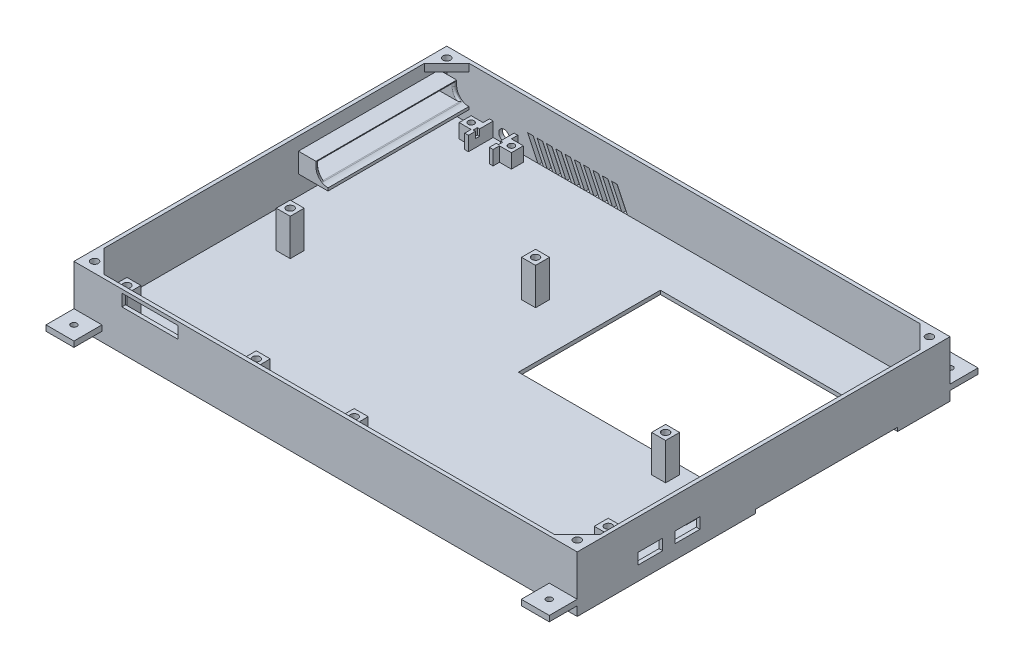
SolidWorks part; units mm, degrees
material "PLA"
ref_plane "Спереди" through (0, 0, 0) normal (0, 0, 1) x (1, 0, 0)
ref_plane "Сверху" through (0, 0, 0) normal (0, 1, 0) x (1, 0, 0)
ref_plane "Справа" through (0, 0, 0) normal (1, 0, 0) x (0, 0, -1)
sketch "Эскиз1" plane through (0, 0, 0) normal (0, 1, 0) x (1, 0, 0)
  line L1 (135, 100) -> (-135, 100)
  line L2 (135, 100) -> (135, -100)
  line L3 (135, -100) -> (-135, -100)
  line L4 (-135, 100) -> (-135, -100)
  line L5 (135, 100) -> (-135, -100) construction
  line L6 (135, -100) -> (-135, 100) construction
  point P0 (0, 0)
  dimension "D1" = 200
  dimension "D2" = 270
extrude "Бобышка-Вытянуть1" add sketch "Эскиз1" along normal blind 2
sketch "Эскиз2" plane through (0, 2, 0) normal (0, 1, 0) x (1, 0, 0)
  line L0 (133, 98) -> (-133, 98)
  line L1 (-133, 98) -> (-133, -98)
  line L2 (-133, -98) -> (-109.3, -98)
  line L3 (133, -98) -> (133, 98)
  line L4 (-135, 100) -> (-135, -100)
  line L5 (-135, -100) -> (135, -100)
  line L6 (135, -100) -> (135, 100)
  line L7 (135, 100) -> (-135, 100)
  line L8 (-135, 100) -> (-135, -100)
  line L9 (-135, -100) -> (-109.3, -100)
  line L10 (135, -100) -> (135, 100)
  line L11 (135, 100) -> (-135, 100)
  line L12 (-109.3, -98) -> (-109.3, -100)
  line L14 (-79.1, -98) -> (-79.1, -100)
  line L16 (-79.1, -98) -> (133, -98)
  line L17 (-79.1, -100) -> (135, -100)
  line L18 (-133, -98) -> (133, -98) construction
  line L20 (-135, -100) -> (135, -100) construction
  dimension "D3" = 25.7
  dimension "D4" = 55.9
  dimension "D1" = 0
  dimension "D2" = 2
extrude "Бобышка-Вытянуть2" add sketch "Эскиз2" along normal offset from surface (28 mm away) 7 offset beyond the face yes
sketch "Эскиз3" plane through (0, 2, 0) normal (0, 1, 0) x (1, 0, 0)
  line L1 (-109.3, -98) -> (-79.1, -98)
  line L2 (-109.3, -98) -> (-109.3, -100)
  line L3 (-109.3, -100) -> (-79.1, -100)
  line L4 (-79.1, -98) -> (-79.1, -100)
extrude "Бобышка-Вытянуть3" add sketch "Эскиз3" along normal blind 19.7
sketch "Эскиз4" plane through (-109.3, 0, 0) normal (1, 0, 0) x (0, 0, -1)
  line L0 (-100, 30) -> (-100, 21.7) construction
  line L1 (-98, 30) -> (-100, 30)
  line L2 (-98, 30) -> (-98, 28.1)
  line L3 (-98, 28.1) -> (-100, 28.1)
  line L4 (-100, 30) -> (-100, 28.1)
  dimension "D1" = 1.9
extrude "Бобышка-Вытянуть4" add sketch "Эскиз4" along normal up to surface (30.2 mm away) up to face at (-79.1, 25.85, 99)
sketch "Эскиз5" plane through (135, 0, 0) normal (1, 0, 0) x (0, 0, -1)
  line L0 (-100, 30) -> (-100, 0) construction
  line L1 (-54.15, 13.5) -> (-67.45, 13.5)
  line L2 (-54.15, 13.5) -> (-54.15, 7.6)
  line L3 (-54.15, 7.6) -> (-67.45, 7.6)
  line L4 (-67.45, 13.5) -> (-67.45, 7.6)
  line L5 (-54.15, 13.5) -> (-67.45, 7.6) construction
  line L6 (-54.15, 7.6) -> (-67.45, 13.5) construction
  line L7 (-34.15, 13.5) -> (-47.45, 13.5)
  line L8 (-34.15, 13.5) -> (-34.15, 7.6)
  line L9 (-34.15, 7.6) -> (-47.45, 7.6)
  line L10 (-47.45, 13.5) -> (-47.45, 7.6)
  line L11 (-34.15, 13.5) -> (-47.45, 7.6) construction
  line L12 (-34.15, 7.6) -> (-47.45, 13.5) construction
  line L13 (-100, 0) -> (100, 0) construction
  point P0 (-60.8, 10.55)
  point P5 (-40.8, 10.55)
  dimension "D1" = 13.3
  dimension "D2" = 5.9
  dimension "D3" = 6.7
  dimension "D4" = 32.55
  dimension "D5" = 13.5
extrude "Вырез-Вытянуть1" cut sketch "Эскиз5" against normal up to surface (2 mm away) up to face at (133, 16, 0)
sketch "Эскиз10" plane through (0, 2, 0) normal (0, 1, 0) x (1, 0, 0)
  line L0 (133, 98) -> (133, -98) construction
  line L1 (123.675, -22.825) -> (116.175, -22.825)
  line L2 (123.675, -22.825) -> (123.675, -30.325)
  line L3 (123.675, -30.325) -> (116.175, -30.325)
  line L4 (116.175, -22.825) -> (116.175, -30.325)
  line L5 (123.675, -22.825) -> (116.175, -30.325) construction
  line L6 (123.675, -30.325) -> (116.175, -22.825) construction
  line L7 (114.05, -54.9) -> (106.55, -54.9)
  line L8 (114.05, -54.9) -> (114.05, -62.4)
  line L9 (114.05, -62.4) -> (106.55, -62.4)
  line L10 (106.55, -54.9) -> (106.55, -62.4)
  line L11 (114.05, -54.9) -> (106.55, -62.4) construction
  line L12 (114.05, -62.4) -> (106.55, -54.9) construction
  line L13 (114.675, -87.875) -> (107.175, -87.875)
  line L14 (114.675, -87.875) -> (114.675, -95.375)
  line L15 (114.675, -95.375) -> (107.175, -95.375)
  line L16 (107.175, -87.875) -> (107.175, -95.375)
  line L17 (114.675, -87.875) -> (107.175, -95.375) construction
  line L18 (114.675, -95.375) -> (107.175, -87.875) construction
  line L19 (133, -98) -> (-133, -98) construction
  point P0 (119.925, -26.575)
  point P5 (110.3, -58.65)
  point P10 (110.925, -91.625)
  dimension "D1" = 13.075
  dimension "D2" = 71.425
  dimension "D3" = 22.7
  dimension "D4" = 39.35
  dimension "D5" = 22.075
  dimension "D6" = 6.375
  dimension "D7" = 7.5
extrude "Бобышка-Вытянуть6" add sketch "Эскиз10" along normal blind 6.9
sketch "Эскиз11" plane through (0, 2, 0) normal (0, 1, 0) x (1, 0, 0)
  line L1 (-45.3446, -84.35) -> (-52.8446, -84.35)
  line L2 (-45.3446, -84.35) -> (-45.3446, -91.85)
  line L3 (-45.3446, -91.85) -> (-52.8446, -91.85)
  line L4 (-52.8446, -84.35) -> (-52.8446, -91.85)
  line L5 (-45.3446, -84.35) -> (-52.8446, -91.85) construction
  line L6 (-45.3446, -91.85) -> (-52.8446, -84.35) construction
  line L7 (-17.6224, 30.2491) -> (-25.1224, 30.2491)
  line L8 (-17.6224, 30.2491) -> (-17.6224, 37.7491)
  line L9 (-17.6224, 37.7491) -> (-25.1224, 37.7491)
  line L10 (-25.1224, 30.2491) -> (-25.1224, 37.7491)
  line L11 (-17.6224, 30.2491) -> (-25.1224, 37.7491) construction
  line L12 (-17.6224, 37.7491) -> (-25.1224, 30.2491) construction
  line L13 (-114.1446, -92.4424) -> (-121.6446, -92.4424)
  line L14 (-114.1446, -92.4424) -> (-114.1446, -84.9424)
  line L15 (-114.1446, -84.9424) -> (-121.6446, -84.9424)
  line L16 (-121.6446, -92.4424) -> (-121.6446, -84.9424)
  line L17 (-114.1446, -92.4424) -> (-121.6446, -84.9424) construction
  line L18 (-114.1446, -84.9424) -> (-121.6446, -92.4424) construction
  line L19 (-106.25, -12.7324) -> (-113.75, -12.7324)
  line L20 (-106.25, -12.7324) -> (-106.25, -5.2324)
  line L21 (-106.25, -5.2324) -> (-113.75, -5.2324)
  line L22 (-113.75, -12.7324) -> (-113.75, -5.2324)
  line L23 (-106.25, -12.7324) -> (-113.75, -5.2324) construction
  line L24 (-106.25, -5.2324) -> (-113.75, -12.7324) construction
  line L25 (98.6279, -16.2195) -> (91.1279, -16.2195)
  line L26 (98.6279, -16.2195) -> (98.6279, -8.7195)
  line L27 (98.6279, -8.7195) -> (91.1279, -8.7195)
  line L28 (91.1279, -16.2195) -> (91.1279, -8.7195)
  line L29 (98.6279, -16.2195) -> (91.1279, -8.7195) construction
  line L30 (98.6279, -8.7195) -> (91.1279, -16.2195) construction
  line L31 (95.4554, -97.6196) -> (87.9554, -97.6196)
  line L32 (95.4554, -97.6196) -> (95.4554, -90.1196)
  line L33 (95.4554, -90.1196) -> (87.9554, -90.1196)
  line L34 (87.9554, -97.6196) -> (87.9554, -90.1196)
  line L35 (95.4554, -97.6196) -> (87.9554, -90.1196) construction
  line L36 (95.4554, -90.1196) -> (87.9554, -97.6196) construction
  line L37 (7.7554, -92.4285) -> (0.2554, -92.4285)
  line L38 (7.7554, -92.4285) -> (7.7554, -84.9285)
  line L39 (7.7554, -84.9285) -> (0.2554, -84.9285)
  line L40 (0.2554, -92.4285) -> (0.2554, -84.9285)
  line L41 (7.7554, -92.4285) -> (0.2554, -84.9285) construction
  line L42 (7.7554, -84.9285) -> (0.2554, -92.4285) construction
  line L44 (-133, 98) -> (133, 98) construction
  line L45 (-133, -98) -> (-133, 98) construction
  line L47 (133, -98) -> (-133, -98) construction
  line L48 (133, 98) -> (133, -98) construction
  point P0 (-49.0946, -88.1)
  point P5 (-21.3724, 33.9991)
  point P10 (-117.8946, -88.6924)
  point P15 (-110, -8.9824)
  point P20 (94.8779, -12.4695)
  point P25 (91.7054, -93.8696)
  point P30 (4.0054, -88.6785)
  dimension "D1" = 7.5
  dimension "D2" = 64.0009
  dimension "D3" = 111.6276
  dimension "D4" = 106.9824
  dimension "D5" = 23
  dimension "D6" = 9.3076
  dimension "D7" = 15.1054
  dimension "D8" = 9.3215
  dimension "D9" = 128.9946
  dimension "D10" = 9.9
  dimension "D11" = 83.9054
  dimension "D12" = 4.1304
  dimension "D13" = 41.2946
  dimension "D14" = 85.5305
  dimension "D15" = 38.1221
extrude "Бобышка-Вытянуть7" add sketch "Эскиз11" along normal blind 19.7
sketch "Эскиз12" plane through (0, 2, 0) normal (0, 1, 0) x (1, 0, 0)
  line L1 (135, 71.9) -> (7.7, 71.9)
  line L2 (135, 71.9) -> (135, -4.25)
  line L3 (135, -4.25) -> (7.7, -4.25)
  line L4 (7.7, 71.9) -> (7.7, -4.25)
  line L5 (-133, 98) -> (133, 98) construction
  line L6 (135, -100) -> (135, 100) construction
  dimension "D1" = 76.15
  dimension "D2" = 127.3
  dimension "D3" = 26.1
extrude "Вырез-Вытянуть2" cut sketch "Эскиз12" against normal through all
sketch "Эскиз14" plane through (0, 21.7, 0) normal (0, 1, 0) x (1, 0, 0)
  line L0 (-113.75, -5.2324) -> (-106.25, -12.7324) construction
  line L1 (-106.25, -5.2324) -> (-113.75, -12.7324) construction
  line L2 (-17.6224, 37.7491) -> (-25.1224, 30.2491) construction
  line L3 (-25.1224, 37.7491) -> (-17.6224, 30.2491) construction
  line L4 (-121.6446, -84.9424) -> (-114.1446, -92.4424) construction
  line L5 (-114.1446, -84.9424) -> (-121.6446, -92.4424) construction
  line L6 (-52.8446, -84.35) -> (-45.3446, -91.85) construction
  line L7 (-45.3446, -84.35) -> (-52.8446, -91.85) construction
  line L8 (0.2554, -84.9285) -> (7.7554, -92.4285) construction
  line L9 (7.7554, -84.9285) -> (0.2554, -92.4285) construction
  line L10 (95.4554, -90.1196) -> (87.9554, -97.6196) construction
  line L11 (95.4554, -90.1196) -> (87.9554, -90.1196) construction
  line L12 (95.4554, -90.1196) -> (95.4554, -97.6196) construction
  line L13 (95.4554, -97.6196) -> (87.9554, -97.6196) construction
  line L14 (87.9554, -90.1196) -> (87.9554, -97.6196) construction
  line L15 (95.4554, -97.6196) -> (87.9554, -90.1196) construction
  line L22 (98.6279, -8.7195) -> (91.1279, -16.2195) construction
  line L23 (98.6279, -16.2195) -> (91.1279, -8.7195) construction
  circle A0 centre (-21.3724, 33.9991) radius 2
  circle A1 centre (-110, -8.9824) radius 2
  circle A2 centre (-117.8946, -88.6924) radius 2
  circle A3 centre (-49.0946, -88.1) radius 2
  circle A4 centre (4.0054, -88.6785) radius 2
  circle A5 centre (91.7054, -93.8696) radius 2
  circle A6 centre (94.8779, -12.4695) radius 2
  dimension "D1" = 4
extrude "Вырез-Вытянуть4" cut sketch "Эскиз14" against normal blind 5
sketch "Эскиз15" plane through (0, 8.9, 0) normal (0, 1, 0) x (1, 0, 0)
  line L0 (123.675, -22.825) -> (116.175, -30.325) construction
  line L1 (116.175, -22.825) -> (123.675, -30.325) construction
  line L2 (106.55, -54.9) -> (114.05, -62.4) construction
  line L3 (114.05, -54.9) -> (106.55, -62.4) construction
  line L4 (107.175, -87.875) -> (114.675, -95.375) construction
  line L5 (114.675, -87.875) -> (107.175, -95.375) construction
  circle A0 centre (110.925, -91.625) radius 2
  circle A1 centre (110.3, -58.65) radius 2
  circle A2 centre (119.925, -26.575) radius 2
  dimension "D1" = 4
extrude "Вырез-Вытянуть5" cut sketch "Эскиз15" against normal blind 5
sketch "Эскиз16" plane through (0, 0, -100) normal (0, 0, -1) x (-1, 0, 0)
  line L0 (133, 23) -> (123.6, 23)
  line L1 (133, 30) -> (133, 2) construction
  line L2 (123.6, 23) -> (123.6, 20.4)
  line L3 (117.1, 13.9) -> (133, 13.9)
  line L4 (133, 13.9) -> (133, 23)
  line L5 (133, 2) -> (-133, 2) construction
  arc A0 (123.6, 20.4) -> (117.1, 13.9) centre (117.1, 20.4) cw
  dimension "D3" = 6.5
  dimension "D1" = 9.4
  dimension "D2" = 2.6
  dimension "D4" = 21
  dimension "D5" = 15.9
extrude "Бобышка-Вытянуть8" add sketch "Эскиз16" against normal blind 75.5 from offset 6.0824 offset against normal yes
sketch "Эскиз18" plane through (0, 0, -18.4176) normal (0, 0, 1) x (1, 0, 0)
  line L0 (-135, 22) -> (-123.6, 22)
  line L1 (-135, 30) -> (-135, 0) construction
  line L2 (-123.6, 23) -> (-123.6, 20.4) construction
  line L3 (-123.6, 22) -> (-123.6, 20.4)
  line L4 (-135, 22) -> (-135, 14.9)
  line L5 (-135, 14.9) -> (-120.5641, 14.9)
  line L6 (-133, 23) -> (-123.6, 23) construction
  line L7 (-117.1, 13.9) -> (-133, 13.9) construction
  arc A0 (-123.6, 20.4) -> (-117.1, 13.9) centre (-117.1, 20.4) ccw construction
  arc A1 (-123.6, 20.4) -> (-120.5641, 14.9) centre (-117.1, 20.4) ccw
  dimension "D1" = 1
  dimension "D2" = 1
extrude "Вырез-Вытянуть6" cut sketch "Эскиз18" against normal offset from surface (72.5 mm away) 1.5 from offset 1.5 up to face at (-126.3292, 18.5708, -93.9176) offset against normal yes
fillet "Скругление1" radius 1 6 edges at (-123.6, 21.2, -92.4176) (-123.6, 21.2, -19.9176) (-122.7906, 17.2589, -92.4176) (-120.5641, 14.9, -56.1676) (-122.7906, 17.2589, -19.9176) (-123.6, 22, -56.1676)
sketch "Эскиз19" plane through (0, 0, -18.4176) normal (0, 0, 1) x (1, 0, 0)
  line L0 (-133, 13.9) -> (-133, 12.4)
  line L1 (-133, 30) -> (-133, 2) construction
  line L2 (-133, 13.9) -> (-117.1, 13.9)
  line L3 (-117.1, 13.9) -> (-133, 13.9) construction
  line L4 (-117.1, 13.9) -> (-117.1, 12.4)
  line L5 (-117.1, 12.4) -> (-133, 12.4)
  dimension "D1" = 1.5
extrude "Бобышка-Вытянуть9" add sketch "Эскиз19" against normal up to surface (75.5 mm away) up to face at (-126.3292, 18.5708, -93.9176)
sketch "Эскиз20" plane through (0, 0, -100) normal (0, 0, -1) x (-1, 0, 0)
  line L0 (135, 30) -> (135, 0) construction
  line L1 (89.5705, 13.5) -> (86.5705, 13.5)
  line L3 (83.9, 1.5) -> (80.9, 1.5)
  line L5 (90.9, 13.5) -> (35.9, 1.5) construction
  line L6 (90.9, 1.5) -> (35.9, 13.5) construction
  line L7 (-135, 0) -> (135, 0) construction
  line L8 (35.9, 1.5) -> (41.5705, 13.5)
  line L9 (44.5705, 13.5) -> (38.9, 1.5)
  line L10 (40.9, 1.5) -> (46.5705, 13.5)
  line L11 (49.5705, 13.5) -> (43.9, 1.5)
  line L12 (45.9, 1.5) -> (51.5705, 13.5)
  line L13 (54.5705, 13.5) -> (48.9, 1.5)
  line L14 (50.9, 1.5) -> (56.5705, 13.5)
  line L15 (59.5705, 13.5) -> (53.9, 1.5)
  line L16 (55.9, 1.5) -> (61.5705, 13.5)
  line L17 (64.5705, 13.5) -> (58.9, 1.5)
  line L18 (60.9, 1.5) -> (66.5705, 13.5)
  line L19 (69.5705, 13.5) -> (63.9, 1.5)
  line L20 (65.9, 1.5) -> (71.5705, 13.5)
  line L21 (74.5705, 13.5) -> (68.9, 1.5)
  line L22 (70.9, 1.5) -> (76.5705, 13.5)
  line L23 (79.5705, 13.5) -> (73.9, 1.5)
  line L24 (75.9, 1.5) -> (81.5705, 13.5)
  line L25 (84.5705, 13.5) -> (78.9, 1.5)
  line L26 (80.9, 1.5) -> (86.5705, 13.5)
  line L27 (89.5705, 13.5) -> (83.9, 1.5)
  line L28 (44.5705, 13.5) -> (41.5705, 13.5)
  line L29 (38.9, 1.5) -> (35.9, 1.5)
  line L30 (43.9, 1.5) -> (40.9, 1.5)
  line L31 (49.5705, 13.5) -> (46.5705, 13.5)
  line L32 (54.5705, 13.5) -> (51.5705, 13.5)
  line L33 (48.9, 1.5) -> (45.9, 1.5)
  line L34 (53.9, 1.5) -> (50.9, 1.5)
  line L35 (59.5705, 13.5) -> (56.5705, 13.5)
  line L36 (58.9, 1.5) -> (55.9, 1.5)
  line L37 (64.5705, 13.5) -> (61.5705, 13.5)
  line L38 (63.9, 1.5) -> (60.9, 1.5)
  line L39 (69.5705, 13.5) -> (66.5705, 13.5)
  line L40 (68.9, 1.5) -> (65.9, 1.5)
  line L41 (74.5705, 13.5) -> (71.5705, 13.5)
  line L42 (73.9, 1.5) -> (70.9, 1.5)
  line L43 (79.5705, 13.5) -> (76.5705, 13.5)
  line L44 (78.9, 1.5) -> (75.9, 1.5)
  line L45 (84.5705, 13.5) -> (81.5705, 13.5)
  line L46 (35.9, 13.5) -> (35.9, 1.5) construction
  line L47 (90.9, 13.5) -> (90.9, 1.5) construction
  point P0 (63.4, 7.5)
  dimension "D1" = 71.6
  dimension "D2" = 1.5
  dimension "D3" = 12
  dimension "D4" = 55
  dimension "D5" = 3
  dimension "D8" = 2
  dimension "D9" = 64.707
  dimension "D6" = 10
extrude "Вырез-Вытянуть7" cut sketch "Эскиз20" against normal up to surface (2 mm away) up to face at (0, 16, -98)
sketch "Эскиз21" plane through (0, 0, -100) normal (0, 0, -1) x (-1, 0, 0)
  line L0 (135, 30) -> (135, 0) construction
  line L1 (-135, 0) -> (135, 0) construction
  circle A0 centre (102.2, 5.825) radius 2.9
  dimension "D1" = 5.8
  dimension "D2" = 32.8
  dimension "D3" = 5.825
extrude "Вырез-Вытянуть8" cut sketch "Эскиз21" against normal up to surface (2 mm away) up to face at (-57.1394, 8.5, -98)
sketch "Эскиз22" plane through (0, 2, 0) normal (0, 1, 0) x (1, 0, 0)
  line L0 (-133, 98) -> (-84.1363, 98) construction
  line L1 (-108.1, 98) -> (-110.1, 98)
  line L2 (-108.1, 98) -> (-108.1, 84.75)
  line L3 (-108.1, 84.75) -> (-110.1, 84.75)
  line L4 (-110.1, 98) -> (-110.1, 84.75)
  line L5 (-133, -98) -> (-133, 98) construction
  line L7 (-94.9, 98) -> (-96.9, 98)
  line L8 (-94.9, 98) -> (-94.9, 84.75)
  line L9 (-94.9, 84.75) -> (-96.9, 84.75)
  line L10 (-96.9, 98) -> (-96.9, 84.75)
  dimension "D1" = 24.9
  dimension "D2" = 13.25
  dimension "D3" = 2
  dimension "D4" = 36.1
extrude "Бобышка-Вытянуть10" add sketch "Эскиз22" along normal blind 7.65
sketch "Эскиз23" plane through (0, 9.65, 0) normal (0, 1, 0) x (1, 0, 0)
  line L0 (-108.1, 84.75) -> (-108.1, 98) construction
  line L1 (-108.1, 90.7) -> (-109.3, 90.7)
  line L2 (-108.1, 90.7) -> (-108.1, 88.5)
  line L3 (-108.1, 88.5) -> (-109.3, 88.5)
  line L4 (-109.3, 90.7) -> (-109.3, 88.5)
  line L5 (-96.9, 98) -> (-96.9, 84.75) construction
  line L6 (-96.9, 90.7) -> (-95.7, 90.7)
  line L7 (-96.9, 90.7) -> (-96.9, 88.5)
  line L8 (-96.9, 88.5) -> (-95.7, 88.5)
  line L9 (-95.7, 90.7) -> (-95.7, 88.5)
  line L10 (-110.1, 84.75) -> (-108.1, 84.75) construction
  dimension "D1" = 2.2
  dimension "D2" = 1.2
  dimension "D3" = 5.95
extrude "Вырез-Вытянуть9" cut sketch "Эскиз23" against normal blind 3.45
sketch "Эскиз24" plane through (0, 2, 0) normal (0, 1, 0) x (1, 0, 0)
  line L0 (-108.6, 91.375) -> (-97.4, 91.375) construction
  line L3 (-102.5, 91.875) -> (-102.5, 50091.875) construction
  line L4 (-108.1, 84.75) -> (-108.1, 98) construction
  line L5 (-108.1, 98) -> (-96.9, 98) construction
  line L6 (-110.1, 98) -> (-110.1, 84.75) construction
  line L7 (-116.5, 94.575) -> (-110.1, 94.575)
  line L8 (-116.5, 94.575) -> (-116.5, 88.175)
  line L9 (-116.5, 88.175) -> (-110.1, 88.175)
  line L10 (-110.1, 94.575) -> (-110.1, 88.175)
  line L11 (-116.5, 94.575) -> (-110.1, 88.175) construction
  line L12 (-116.5, 88.175) -> (-110.1, 94.575) construction
  line L13 (-88.5, 88.175) -> (-94.9, 88.175)
  line L14 (-94.9, 94.575) -> (-94.9, 88.175)
  line L15 (-88.5, 94.575) -> (-94.9, 94.575)
  line L16 (-88.5, 94.575) -> (-88.5, 88.175)
  circle A0 centre (-113.3, 91.375) radius 1.7 construction
  point P3 (-108.1, 91.375)
  point P8 (-102.5, 98)
  point P10 (-113.3, 91.375)
  dimension "D1" = 3.4
  dimension "D2" = 1.5
extrude "Бобышка-Вытянуть11" add sketch "Эскиз24" along normal up to surface (7.65 mm away) up to face at (-108.9, 9.65, -90.4875)
sketch "Эскиз25" plane through (0, 9.65, 0) normal (0, 1, 0) x (1, 0, 0)
  line L0 (-116.5, 94.575) -> (-110.1, 88.175) construction
  line L1 (-110.1, 94.575) -> (-116.5, 88.175) construction
  line L2 (-94.9, 94.575) -> (-88.5, 88.175) construction
  line L3 (-88.5, 94.575) -> (-94.9, 88.175) construction
  circle A0 centre (-113.3, 91.375) radius 1.65
  circle A1 centre (-91.7, 91.375) radius 1.65
  dimension "D1" = 3.3
extrude "Вырез-Вытянуть10" cut sketch "Эскиз25" against normal blind 3
sketch "Эскиз26" plane through (0, 30, 0) normal (0, 1, 0) x (1, 0, 0)
  line L0 (0, 0) -> (0, 50000) construction
  line L1 (0, 0) -> (-50000, 0) construction
  line L2 (121, 98) -> (133, 98)
  line L3 (-36.1363, 98) -> (133, 98) construction
  line L4 (133, 98) -> (133, 86)
  line L5 (133, 98) -> (133, -98) construction
  line L6 (133, 86) -> (121, 98)
  line L7 (133, 98) -> (127, 92) construction
  line L8 (133, -98) -> (133, -86)
  line L9 (121, -98) -> (133, -98)
  line L10 (133, -86) -> (121, -98)
  line L11 (-121, -98) -> (-133, -98)
  line L12 (-133, -86) -> (-121, -98)
  line L13 (-133, -98) -> (-133, -86)
  line L14 (-133, 98) -> (-133, 86)
  line L15 (-121, 98) -> (-133, 98)
  line L16 (-133, 86) -> (-121, 98)
  circle A0 centre (129.5102, 94.5102) radius 2.05 construction
  dimension "D1" = 4.1
  dimension "D3" = 1.5
  dimension "D4" = 1.4398
  dimension "D2" = 12
extrude "Бобышка-Вытянуть12" add sketch "Эскиз26" against normal blind 4
sketch "Эскиз27" plane through (0, 30, 0) normal (0, 1, 0) x (1, 0, 0)
  line L0 (0, 0) -> (0, 50000) construction
  line L1 (0, 0) -> (-50000, 0) construction
  line L2 (135, 100) -> (127, 92) construction
  line L3 (121, 98) -> (133, 86) construction
  circle A0 centre (129.4749, 94.4749) radius 2
  circle A1 centre (129.4749, -94.4749) radius 2
  circle A2 centre (-129.4749, -94.4749) radius 2
  circle A3 centre (-129.4749, 94.4749) radius 2
  dimension "D1" = 4
  dimension "D2" = 1.5
extrude "Вырез-Вытянуть11" cut sketch "Эскиз27" against normal up to surface (4 mm away) up to face at (129, 26, -94)
sketch "Эскиз28" plane through (0, 0, -100) normal (0, 0, -1) x (-1, 0, 0)
  line L0 (-135, 30) -> (-135, 0) construction
  line L1 (-135, 5) -> (-120, 5)
  line L2 (-135, 5) -> (-135, 8)
  line L3 (-135, 8) -> (-120, 8)
  line L4 (-120, 5) -> (-120, 8)
  line L5 (-135, 0) -> (135, 0) construction
  dimension "D1" = 3
  dimension "D2" = 15
  dimension "D3" = 5
extrude "Бобышка-Вытянуть13" add sketch "Эскиз28" along normal blind 15
sketch "Эскиз29" plane through (0, 8, 0) normal (0, 1, 0) x (1, 0, 0)
  line L0 (120, 115) -> (135, 100) construction
  line L1 (135, 115) -> (120, 100) construction
  circle A0 centre (127.5, 107.5) radius 1.6
  dimension "D1" = 3.2
extrude "Вырез-Вытянуть12" cut sketch "Эскиз29" against normal through all
mirror "Зеркальное отражение1" about plane through (0, 0, 0) normal (0, 0, 1) of "Вырез-Вытянуть12", "Бобышка-Вытянуть13"
mirror "Зеркальное отражение2" about plane through (0, 0, 0) normal (1, 0, 0) of "Зеркальное отражение1"
